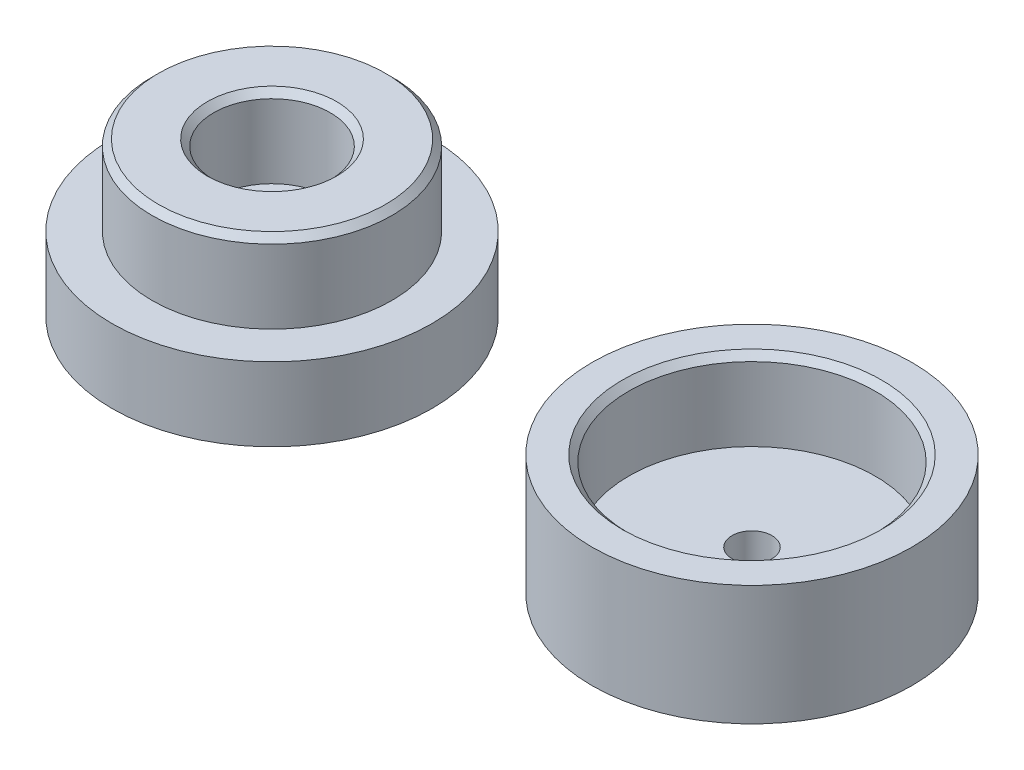
SolidWorks part; units mm, degrees
ref_plane "Front Plane" through (0, 0, 0) normal (0, 0, 1) x (1, 0, 0)
ref_plane "Top Plane" through (0, 0, 0) normal (0, 1, 0) x (1, 0, 0)
ref_plane "Right Plane" through (0, 0, 0) normal (1, 0, 0) x (0, 0, -1)
sketch "Sketch2" plane through (0, 0, 0) normal (0, 1, 0) x (1, 0, 0)
  circle A0 centre (0, 0) radius 6.35
  circle A1 centre (0, 0) radius 4.7625
  circle A2 centre (0, 0) radius 0.7937
  circle A3 centre (0, 0) radius 2.3114
  dimension "D1" = 12.7
  dimension "D2" = 9.525
  dimension "D3" = 1.5875
  dimension "D4" = 4.6228
extrude "Boss-Extrude1" add sketch "Sketch2" along normal blind 2.921 contours A0 A1 | A1 A3 | A3 A2 region at (-6.1704, 0, 0) region at (-4.6278, 0, 0) region at (-2.246, 0, 0)
extrude "Boss-Extrude2" add sketch "Sketch2<3>" along normal blind 3.175 from surface contours A1 A3 region at (-4.6278, 0, 0) starting at face at (0, 2.921, 6.35)
sketch "Sketch2<3>" plane through (0, 0, 0) normal (0, 1, 0) x (1, 0, 0) same geometry as "Sketch2"
chamfer "Chamfer1" distance 0.254 angle 45 2 edges at (0, 6.096, 2.3114) (0, 6.096, 4.7625)
sketch "Sketch3" plane through (0, 0, 0) normal (0, 1, 0) x (1, 0, 0)
  line L0 (0, 0) -> (19.05, 0) construction
  circle A0 centre (19.05, 0) radius 6.35
  circle A1 centre (19.05, 0) radius 4.8895
  circle A2 centre (19.05, 0) radius 0.7937
  dimension "D1" = 12.7
  dimension "D3" = 9.779
  dimension "D4" = 1.5875
  dimension "D2" = 19.05
extrude "Boss-Extrude3" add sketch "Sketch3" along normal blind 1.5875 separate body contours A0 A1 | A1 A2 | A0 region at (12.8796, 0, 0) region at (14.2988, 0, 0)
extrude "Boss-Extrude4" add sketch "Sketch3<3>" along normal blind 3.175 from surface contours A0 A1 region at (12.8796, 0, 0) starting at face at (19.05, 1.5875, 6.35)
sketch "Sketch3<3>" plane through (0, 0, 0) normal (0, 1, 0) x (1, 0, 0) same geometry as "Sketch3"
extrude "Cut-Extrude1" cut sketch "Sketch3<4>" against normal through all both and the other way through all contours A2 region at (19.05, 0, 0)
sketch "Sketch3<4>" plane through (0, 0, 0) normal (0, 1, 0) x (1, 0, 0) same geometry as "Sketch3"
chamfer "Chamfer2" distance 0.254 angle 45 2 edges at (19.05, 0, 0.7937) (19.05, 4.7625, 4.8895)
